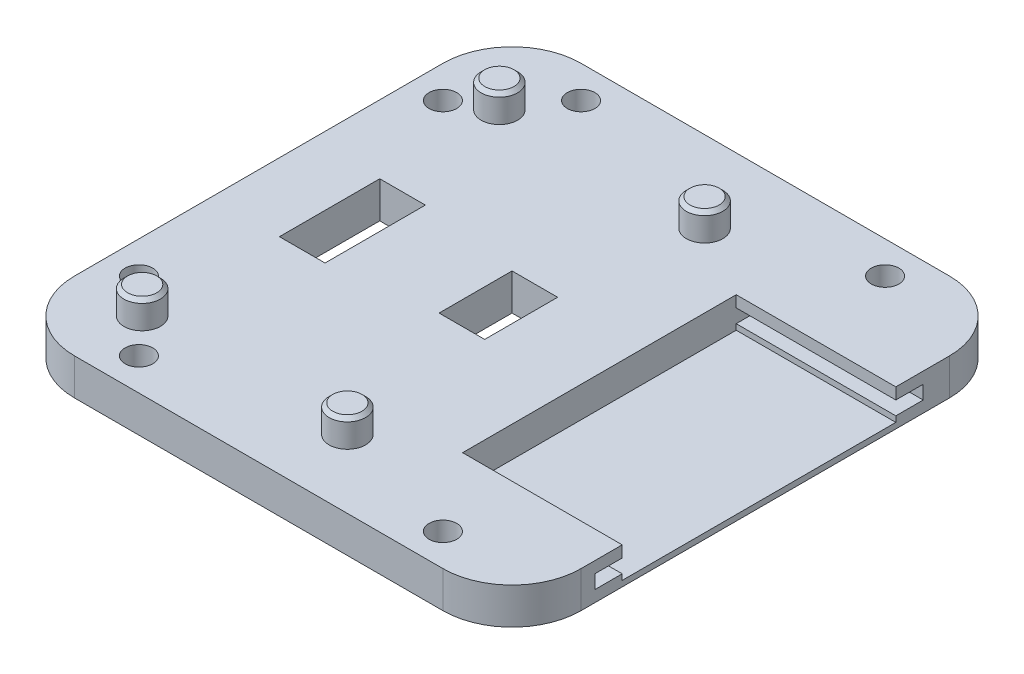
SolidWorks part; units mm, degrees
ref_plane "Front Plane" through (0, 0, 0) normal (0, 0, 1) x (1, 0, 0)
ref_plane "Top Plane" through (0, 0, 0) normal (0, 1, 0) x (1, 0, 0)
ref_plane "Right Plane" through (0, 0, 0) normal (1, 0, 0) x (0, 0, -1)
sketch "Sketch1" plane through (0, 0, 0) normal (0, 1, 0) x (1, 0, 0)
  line L0 (40.0233, 56.9361) -> (-40.7786, 56.9361)
  line L1 (-55.929, 41.7857) -> (-55.929, -39.0162)
  line L2 (-40.7786, -54.1666) -> (40.0233, -54.1666)
  line L3 (55.1737, -39.0162) -> (55.1737, 41.7857)
  line L5 (-30.929, 12.9361) -> (-40.929, 12.9361)
  line L6 (-30.929, 12.9361) -> (-30.929, -9.0639)
  line L7 (-30.929, -9.0639) -> (-40.929, -9.0639)
  line L8 (-40.929, 12.9361) -> (-40.929, -9.0639)
  line L9 (-8.9184, 9.9361) -> (1.0816, 9.9361)
  line L10 (-8.9184, 9.9361) -> (-8.9184, -6.0639)
  line L11 (-8.9184, -6.0639) -> (1.0816, -6.0639)
  line L12 (1.0816, 9.9361) -> (1.0816, -6.0639)
  circle A0 centre (-48.8588, 34.7156) radius 3.0301
  circle A1 centre (-33.7085, 49.8659) radius 3.0301
  arc A2 (55.1737, 41.7857) -> (40.0233, 56.9361) centre (40.0233, 41.7857) ccw
  arc A3 (-40.7786, 56.9361) -> (-55.929, 41.7857) centre (-40.7786, 41.7857) ccw
  arc A4 (-55.929, -39.0162) -> (-40.7786, -54.1666) centre (-40.7786, -39.0162) ccw
  arc A5 (40.0233, -54.1666) -> (55.1737, -39.0162) centre (40.0233, -39.0162) ccw
  circle A6 centre (32.9532, 49.8659) radius 3.0301
  circle A8 centre (-48.8588, -31.9461) radius 3.0301
  circle A9 centre (-33.7085, -47.0964) radius 3.0301
  circle A10 centre (32.9532, -47.0964) radius 3.0301
  dimension "D1" = 22
  dimension "D2" = 10
  dimension "D3" = 44
  dimension "D4" = 15
  dimension "D5" = 16
  dimension "D6" = 10
  dimension "D7" = 47
extrude "Boss-Extrude1" add sketch "Sketch1" along normal blind 8
sketch "Sketch3" plane through (55.1737, 0, 0) normal (1, 0, 0) x (0, 0, -1)
  line L0 (-30, 8) -> (-30, 5.5)
  line L1 (-39.0162, 8) -> (41.7857, 8) construction
  line L2 (-30, 5.5) -> (-36, 5.5)
  line L3 (-36, 5.5) -> (-36, 2.5)
  line L4 (-36, 2.5) -> (-30, 2.5)
  line L5 (-30, 2.5) -> (-30, 1.25)
  line L7 (0, 0) -> (0, 8) construction
  line L8 (30, 2.5) -> (30, 1.25)
  line L9 (36, 2.5) -> (30, 2.5)
  line L10 (36, 5.5) -> (36, 2.5)
  line L11 (30, 5.5) -> (36, 5.5)
  line L12 (30, 8) -> (30, 5.5)
  line L13 (-30, 8) -> (30, 8)
  line L15 (-30, 1.25) -> (30, 1.25)
  dimension "D1" = 30
  dimension "D2" = 30
  dimension "D3" = 6
  dimension "D4" = 3
  dimension "D5" = 2.5
extrude "Cut-Extrude1" cut sketch "Sketch3" against normal blind 35
sketch "Sketch4" plane through (0, 8, 0) normal (0, 1, 0) x (1, 0, 0)
  line L0 (-40.7786, -54.1666) -> (40.0233, -54.1666) construction
  line L1 (-55.929, 41.7857) -> (-55.929, -39.0162) construction
  circle A0 centre (4.071, -39.1666) radius 4
  circle A1 centre (-40.929, -39.1666) radius 4
  dimension "D1" = 8
  dimension "D2" = 8
  dimension "D3" = 45
  dimension "D4" = 15
  dimension "D5" = 15
extrude "Boss-Extrude2" add sketch "Sketch4" along normal blind 6
chamfer "Chamfer1" distance 0.8 angle 45 2 edges at (4.071, 14, 43.1666) (-40.929, 14, 43.1666)
mirror "Mirror1" about plane through (0, 0, 0) normal (0, 0, 1) of "Chamfer1", "Boss-Extrude2"
